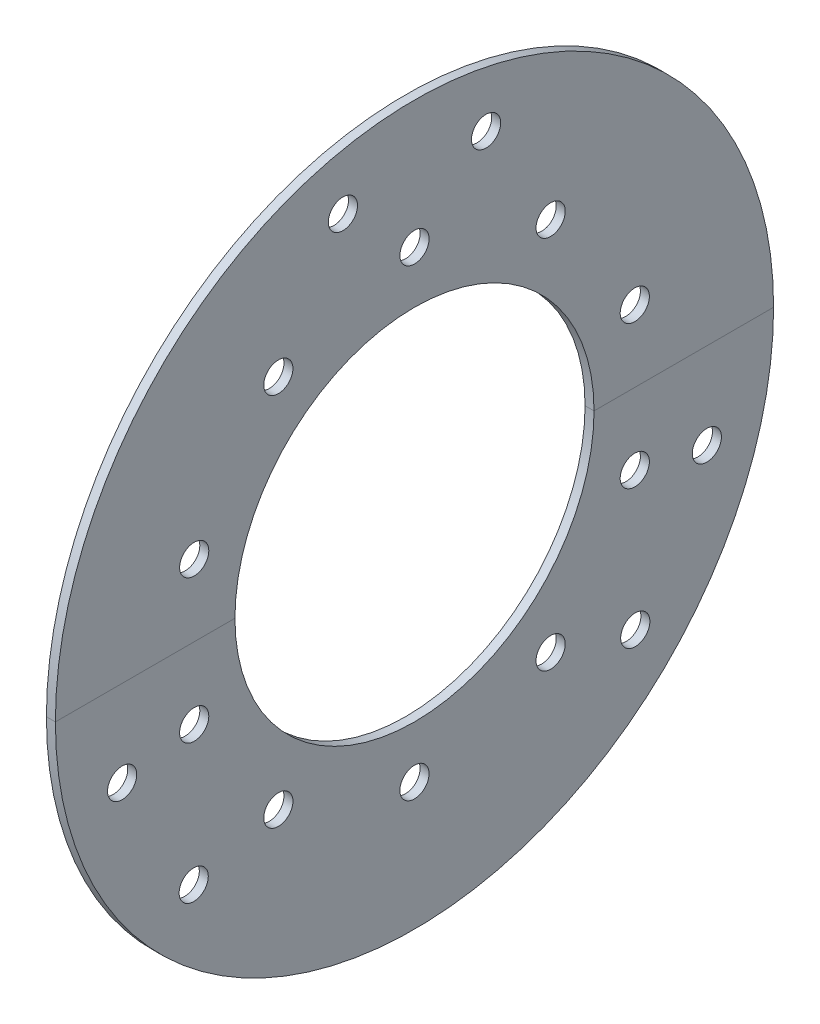
SolidWorks part; units mm, degrees
ref_plane "Front Plane" through (0, 0, 0) normal (0, 0, 1) x (1, 0, 0)
ref_plane "Top Plane" through (0, 0, 0) normal (0, 1, 0) x (1, 0, 0)
ref_plane "Right Plane" through (0, 0, 0) normal (1, 0, 0) x (0, 0, -1)
sketch "Sketch1" plane through (0, 0, 0) normal (1, 0, 0) x (0, 0, -1)
  line L0 (0, 0) -> (0, 66) construction
  line L1 (-15.9453, 66) -> (15.9453, 66) construction
  line L2 (0, 0) -> (0, 51.6) construction
  circle A0 centre (0, 0) radius 80
  circle A1 centre (0, 0) radius 40
  circle A2 centre (30.3297, 41.7453) radius 3.25
  circle A3 centre (49.0745, 15.9453) radius 3.25
  circle A4 centre (49.0745, -15.9453) radius 3.25
  circle A5 centre (30.3297, -41.7453) radius 3.25
  circle A6 centre (0, -51.6) radius 3.25
  circle A7 centre (-30.3297, -41.7453) radius 3.25
  circle A8 centre (-49.0745, -15.9453) radius 3.25
  circle A10 centre (-49.0745, 15.9453) radius 3.25
  circle A11 centre (-30.3297, 41.7453) radius 3.25
  circle A12 centre (0, 51.6) radius 3.25
  circle A22 centre (-15.9453, 66) radius 3.25
  circle A23 centre (15.9453, 66) radius 3.25
  circle A24 centre (65.1303, -19.191) radius 3.25
  circle A25 centre (49.185, -46.809) radius 3.25
  circle A26 centre (-49.185, -46.809) radius 3.25
  circle A27 centre (-65.1303, -19.191) radius 3.25
  point P29 (0, 0)
  point P37 (0, 66)
  point P51 (0, 0)
  dimension "OuterDia" = 160
  dimension "InnerDia" = 80
  dimension "D5" = 6.5
  dimension "D7" = 6.5
  dimension "BoltHoleDia" = 6.5
  dimension "OuterHoleOffset" = 66
  dimension "OuterHoleSpacing" = 31.8906
  dimension "InnerHoleOffset" = 51.6
  dimension "D2" = 31.8906
  dimension "D8" = 3
  dimension "D10" = 10
extrude "Boss-Extrude1" add sketch "Sketch1" along normal blind 2
ref_plane "Plane1" through (0, 0, 0) normal (0, 1, 0) x (1, 0, 0)
split "Split1" trim tools "Plane1" bodies to split 102 resulting bodies 103 104
equation "\"D5@Sketch1\"=\"BoltHoleDia@Sketch1\""
equation "\"D7@Sketch1\"=\"BoltHoleDia@Sketch1\""
equation "\"OuterHoleSpacing@Sketch1\"=\"D2@Sketch1\""
